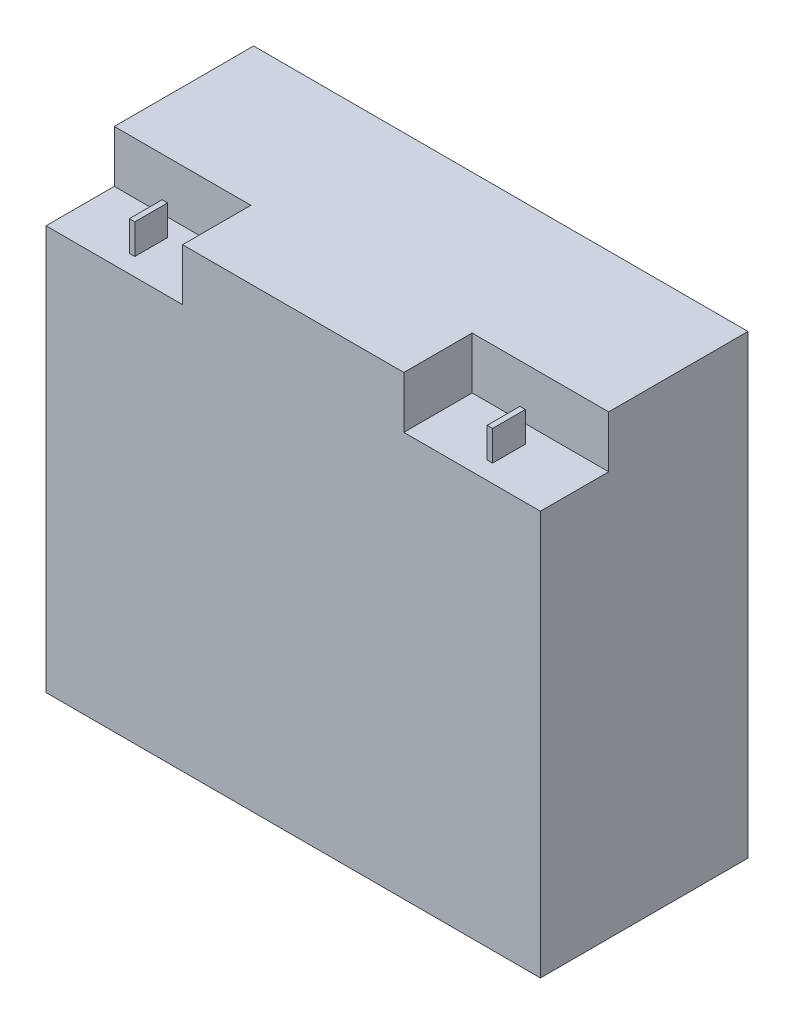
SolidWorks part; units mm, degrees
material "ALUMINUM 6061-T6"
ref_plane "Front Plane" through (0, 0, 0) normal (0, 0, 1) x (1, 0, 0)
ref_plane "Top Plane" through (0, 0, 0) normal (0, 1, 0) x (1, 0, 0)
ref_plane "Right Plane" through (0, 0, 0) normal (1, 0, 0) x (0, 0, -1)
sketch "Sketch1" plane through (0, 0, 0) normal (0, 0, 1) x (1, 0, 0)
  line L1 (-90.5, -83.5) -> (90.5, -83.5)
  line L2 (-90.5, -83.5) -> (-90.5, 83.5)
  line L3 (-90.5, 83.5) -> (90.5, 83.5)
  line L4 (90.5, -83.5) -> (90.5, 83.5)
  line L5 (-90.5, -83.5) -> (90.5, 83.5) construction
  line L6 (-90.5, 83.5) -> (90.5, -83.5) construction
  point P0 (0, 0)
  dimension "D1" = 181
  dimension "D2" = 167
extrude "Boss-Extrude1" add sketch "Sketch1" along normal mid plane 76
sketch "Sketch2" plane through (0, 0, 38) normal (0, 0, 1) x (1, 0, 0)
  text T0 "ES17-12" height 20
sketch "Sketch3" plane through (0, 0, 38) normal (0, 0, 1) x (1, 0, 0)
  line L1 (-90.5, 83.5) -> (-40.5, 83.5)
  line L2 (-90.5, 83.5) -> (-90.5, 64.5)
  line L3 (-90.5, 64.5) -> (-40.5, 64.5)
  line L4 (-40.5, 83.5) -> (-40.5, 64.5)
  line L5 (90.5, 83.5) -> (40.5, 83.5)
  line L6 (90.5, 83.5) -> (90.5, 64.5)
  line L7 (90.5, 64.5) -> (40.5, 64.5)
  line L8 (40.5, 83.5) -> (40.5, 64.5)
  dimension "D1" = 19
  dimension "D2" = 50
  dimension "D3" = 19
  dimension "D4" = 50
extrude "Cut-Extrude1" cut sketch "Sketch3" against normal blind 25
sketch "Sketch4" plane through (0, 64.5, 0) normal (0, 1, 0) x (1, 0, 0)
  line L0 (-65.5, -31.5) -> (-65.5, -38) construction
  line L1 (-66.5, -19.5) -> (-64.5, -19.5)
  line L2 (-66.5, -19.5) -> (-66.5, -31.5)
  line L3 (-66.5, -31.5) -> (-64.5, -31.5)
  line L4 (-64.5, -19.5) -> (-64.5, -31.5)
  line L5 (64.5, -19.5) -> (66.5, -19.5)
  line L6 (64.5, -19.5) -> (64.5, -31.5)
  line L7 (64.5, -31.5) -> (66.5, -31.5)
  line L8 (66.5, -19.5) -> (66.5, -31.5)
  line L9 (-90.5, -38) -> (-40.5, -38) construction
  line L10 (65.5, -31.5) -> (65.5, -38) construction
  line L11 (40.5, -38) -> (90.5, -38) construction
  line L12 (-65.5, -19.5) -> (-65.5, -13) construction
  line L13 (-90.5, -13) -> (-40.5, -13) construction
  dimension "D1" = 2
  dimension "D2" = 12
extrude "Boss-Extrude2" add sketch "Sketch4" along normal blind 11
